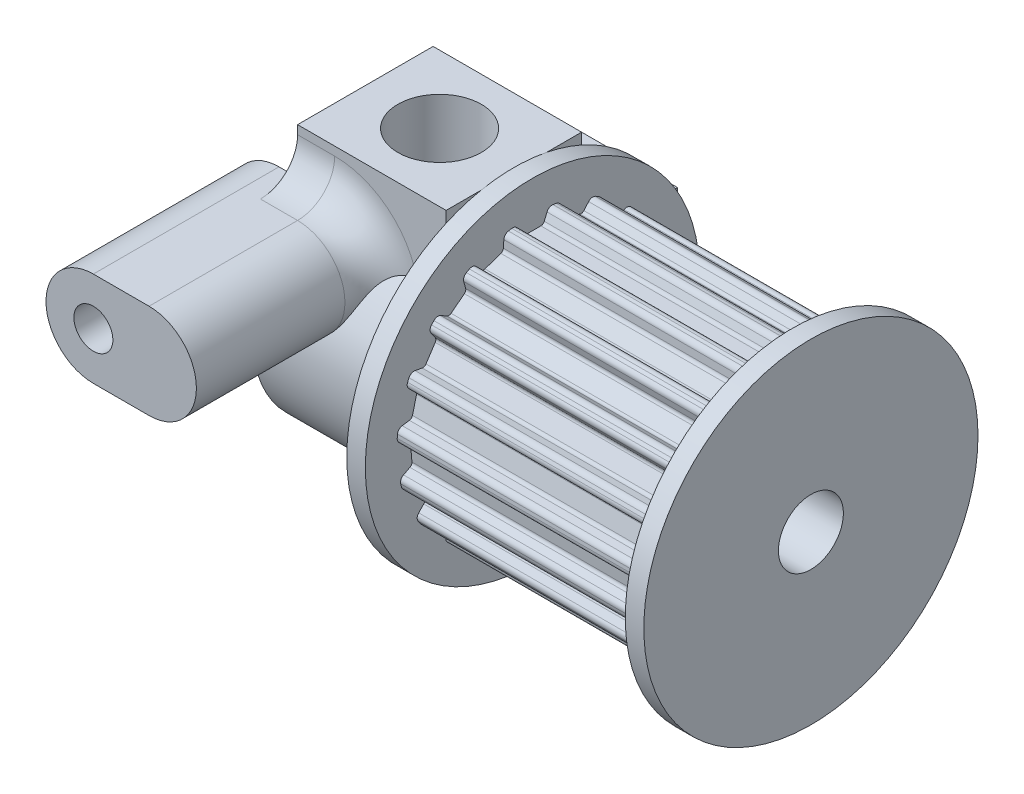
SolidWorks part; units mm, degrees
material "PLA Black"
ref_plane "Front" through (0, 0, 0) normal (0, 0, 1) x (1, 0, 0)
ref_plane "Top" through (0, 0, 0) normal (0, 1, 0) x (1, 0, 0)
ref_plane "Right" through (0, 0, 0) normal (1, 0, 0) x (0, 0, -1)
sketch "Sketch1" plane through (0, 0, 0) normal (1, 0, 0) x (0, 0, -1)
  line L0 (1.118, 1) -> (-1.118, 1) construction
  line L1 (-3.65, 4.8249) -> (3.65, 4.8249)
  line L2 (4.8249, 3.65) -> (4.8249, -3.65)
  line L3 (0, 0) -> (11.6334, 0) construction
  line L4 (0, 0) -> (0, 8.6732) construction
  arc A0 (-1.118, 1) -> (1.118, 1) centre (0, 0) ccw construction
  circle A1 centre (0, 0) radius 1.75
  arc A2 (4.8249, -3.65) -> (-3.65, 4.8249) centre (0, 0) cw
  arc A3 (4.8249, 3.65) -> (3.65, 4.8249) centre (0, 0) ccw
  dimension "D1" = 3
  dimension "D3" = 0.25
  dimension "D5" = 6.05
  dimension "D2" = 1
  dimension "D4" = 7.3
extrude "Boss-Extrude1" add sketch "Sketch1" along normal mid plane 8
sketch "Sketch2" plane through (0, 4.8249, 0) normal (0, 1, 0) x (1, 0, 0)
  circle A0 centre (0, 0) radius 2.25
  dimension "D1" = 4.5
extrude "Cut-Extrude1" cut sketch "Sketch2" against normal blind 5
sketch "Sketch7" plane through (4, 0, 0) normal (1, 0, 0) x (0, 0, -1)
  circle A0 centre (0, 0) radius 1.75 construction
  circle A1 centre (0, 0) radius 7.3
  circle A2 centre (0, 0) radius 1.75
  dimension "D1" = 14.6
extrude "Boss-Extrude5" add sketch "Sketch7" along normal blind 15
sketch "Sketch8" plane through (19, 0, 0) normal (1, 0, 0) x (0, 0, -1)
  line L0 (-0.4541, 6.5499) -> (0.4528, 6.5499)
  line L1 (0.6374, 6.6734) -> (0.7865, 7.0333)
  line L2 (-0.6389, 6.6734) -> (-0.788, 7.0333)
  line L6 (0, 9.2013) -> (0, 0) construction
  arc A0 (0.4528, 6.5499) -> (0.6374, 6.6734) centre (0.4526, 6.7499) ccw
  arc A1 (-0.4541, 6.5499) -> (-0.6389, 6.6734) centre (-0.4541, 6.7499) cw
  arc A2 (0.7865, 7.0333) -> (1.1093, 7.2152) centre (1.0638, 6.9187) cw
  arc A3 (-0.788, 7.0333) -> (-1.1108, 7.215) centre (-1.0652, 6.9185) ccw
  circle A4 centre (0, 0) radius 7.3 construction
  arc A5 (-1.1108, 7.215) -> (1.1093, 7.2152) centre (0, 0) cw
  point P3 (-0.0007, 6.5499)
  point P15 (0, 9.84)
extrude "Cut-Extrude3" cut sketch "Sketch8" against normal up to surface (15 mm away) up to face at (4, 0, -7.3)
pattern_circular "CirPattern1" count 19 over 360 about axis through (19, 0, 0) along (-1, 0, 0) of "Cut-Extrude3"
sketch "Sketch9" plane through (19, 0, 0) normal (1, 0, 0) x (0, 0, -1)
  circle A0 centre (0, 0) radius 9
  circle A1 centre (0, 0) radius 1.75 construction
  circle A2 centre (0, 0) radius 1.75
  dimension "D1" = 18
extrude "Boss-Extrude6" add sketch "Sketch9" along normal blind 1
sketch "Sketch10" plane through (4, 0, 0) normal (-1, 0, 0) x (0, 0, 1)
  circle A0 centre (0, 0) radius 9
  circle A1 centre (0, 0) radius 9 construction
  circle A2 centre (0, 0) radius 1.75 construction
  circle A3 centre (0, 0) radius 1.75
extrude "Boss-Extrude7" add sketch "Sketch10" against normal blind 1
sketch "Sketch3" plane through (0, 0, -4.8249) normal (0, 0, -1) x (-1, 0, 0)
  circle A0 centre (0, 0) radius 2.25
  dimension "D1" = 4.5
extrude "Cut-Extrude2" cut sketch "Sketch3" against normal blind 5
sketch "Sketch4" plane through (0, 4.8249, 0) normal (0, 1, 0) x (1, 0, 0)
  line L0 (4, 3.65) -> (-4, 3.65) construction
  line L2 (4, -3.65) -> (-4, -3.65) construction
  line L3 (-4, 3.65) -> (-4, -3.65) construction
  line L4 (4, 3.65) -> (-4, 3.65)
  line L5 (4, 3.65) -> (4, -3.65)
  line L6 (4, -3.65) -> (-4, -3.65)
  line L7 (-4, 3.65) -> (-4, -3.65)
  line L8 (4, 7.3) -> (4, -7.3) construction
  circle A0 centre (0, 0) radius 2.25 construction
  circle A1 centre (0, 0) radius 2.25
extrude "Boss-Extrude2" add sketch "Sketch4" along normal blind 4
sketch "Sketch5" plane through (0, 0, -4.8249) normal (0, 0, -1) x (-1, 0, 0)
  line L0 (-4, 3.65) -> (4, 3.65) construction
  line L1 (4, -3.65) -> (4, 3.65) construction
  line L2 (-4, -3.65) -> (4, -3.65) construction
  line L4 (-4, 3.65) -> (4, 3.65)
  line L5 (4, -3.65) -> (4, 3.65)
  line L6 (-4, -3.65) -> (4, -3.65)
  line L7 (-4, -3.65) -> (-4, 3.65)
  line L8 (-4, -7.3) -> (-4, 7.3) construction
  circle A0 centre (0, 0) radius 2.25 construction
  circle A1 centre (0, 0) radius 2.25
extrude "Boss-Extrude3" add sketch "Sketch5" along normal blind 4
ref_axis "Axis1" through (20, 0, 0) along (-1, 0, 0)
sketch "Sketch6" plane through (0, 0, 3.65) normal (0, 0, 1) x (1, 0, 0)
  line L0 (-4, 8.8249) -> (-4, 4.8249) construction
  line L2 (-2, 6.3555) -> (-5, 6.3555)
  line L3 (-5, 1.2545) -> (-2, 1.2545)
  line L6 (20, 0) -> (-4, 0) construction
  circle A0 centre (-5, 3.805) radius 1.0505
  arc A1 (-5, 6.3555) -> (-5, 1.2545) centre (-5, 3.805) ccw
  arc A2 (-2, 6.3555) -> (-2, 1.2545) centre (-2, 3.805) cw
  dimension "D1" = 2.101
  dimension "D2" = 3.805
  dimension "D3" = 1.5
  dimension "D4" = 1
  dimension "D5" = 3
extrude "Boss-Extrude4" add sketch "Sketch6" along normal blind 10
fillet "Fillet1" radius 2 2 edges at (-0.6029, 5.9388, 3.65) (-3, 6.3555, 3.65)
equation "\"knee_angle\"= 70"
equation "\"ankle_angle\" = 70"
equation "\"hip_angle\" = 30"
equation "\"spring_ankle_parallel_arm_diameter\"= 1.5"
equation "\"spring_ankle_parallel_arm_length\"= 13"
equation "\"spring_ankle_parallel_intern_diameter\"= 5.7"
equation "\"spring_ankle_parallel_angle\"= \"ankle_angle\""
equation "\"spring_ankle_parallel_turns\"= 3"
equation "\"spring_ankle_parallel_pitch\"= \"spring_ankle_parallel_arm_diameter\" * 1.01"
equation "\"spring_ankle_parallel_cutting_distance\"= (1-\"spring_ankle_parallel_angle\" / 360) * \"spring_ankle_parallel_pitch\""
equation "\"spring_ankle_serial_arm_diameter\"= 1.91"
equation "\"spring_ankle_serial_arm_length\"= 10"
equation "\"spring_ankle_serial_intern_diameter\"= 5.7"
equation "\"spring_ankle_serial_angle\"= \"90\""
equation "\"spring_ankle_serial_turns\"= 3"
equation "\"spring_ankle_serial_pitch\"= \"spring_ankle_serial_arm_diameter\" * 1.01"
equation "\"spring_ankle_serial_cutting_distance\"= (1-\"spring_ankle_serial_angle\" / 360) * \"spring_ankle_serial_pitch\""
equation "\"spring_knee_parallel_arm_diameter\"= 1.5"
equation "\"spring_knee_parallel_arm_length\"= 13"
equation "\"spring_knee_parallel_intern_diameter\"= 5.7"
equation "\"spring_knee_parallel_angle\"= -\"knee_angle\" + 90"
equation "\"spring_knee_parallel_turns\"= 3"
equation "\"spring_knee_parallel_pitch\"= \"spring_knee_parallel_arm_diameter\" * 1.01"
equation "\"spring_knee_parallel_cutting_distance\"= (1-(\"spring_knee_parallel_angle\") / 360) * \"spring_knee_parallel_pitch\""
equation "\"spring_knee_serial_arm_diameter\"= 1.91"
equation "\"spring_knee_serial_arm_length\"= 10"
equation "\"spring_knee_serial_intern_diameter\"= 5.7"
equation "\"spring_knee_serial_angle\"= \"90\""
equation "\"spring_knee_serial_turns\"= 3"
equation "\"spring_knee_serial_pitch\"= \"spring_knee_serial_arm_diameter\" * 1.01"
equation "\"spring_knee_serial_cutting_distance\"= (1-\"spring_knee_serial_angle\" / 360) * \"spring_knee_serial_pitch\""
equation "\"D2@Sketch6\" = ( \"spring_ankle_serial_intern_diameter\" + \"spring_ankle_serial_arm_diameter\" ) / 2"
equation "\"D1@Sketch6\" = \"spring_ankle_serial_arm_diameter\" * 1.1"
